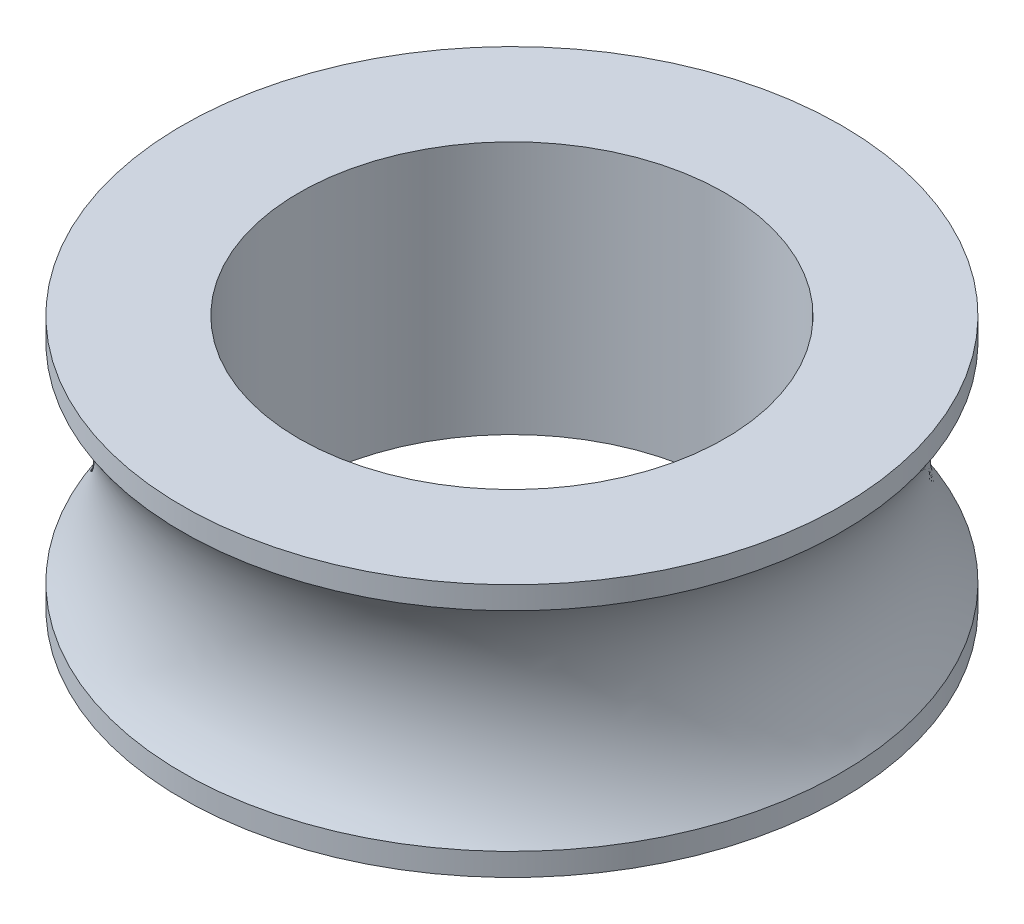
SolidWorks part; units mm, degrees
ref_plane "前视基准面" through (0, 0, 0) normal (0, 0, 1) x (1, 0, 0)
ref_plane "上视基准面" through (0, 0, 0) normal (0, 1, 0) x (1, 0, 0)
ref_plane "右视基准面" through (0, 0, 0) normal (1, 0, 0) x (0, 0, -1)
sketch "草图1" plane through (0, 0, 0) normal (0, 0, 1) x (1, 0, 0)
  line L0 (39, 27.3288) -> (39, 30)
  line L1 (0, 0) -> (39, 0)
  line L2 (0, 0) -> (0, 30)
  line L3 (0, 30) -> (39, 30)
  line L4 (39, 0) -> (39, 2.6712)
  arc A0 (39, 2.6712) -> (39, 27.3288) centre (56, 15) cw
  point P15 (35, 15)
  dimension "D3" = 21
  dimension "D1" = 30
  dimension "D2" = 39
  dimension "D4" = 35
revolve "旋转1" add sketch "草图1" angle 360 about L2
sketch "草图2" plane through (0, 30, 0) normal (0, 1, 0) x (1, 0, 0)
  circle A0 centre (0, 0) radius 25.2
  dimension "D1" = 50.4
extrude "切除-拉伸1" cut sketch "草图2" against normal through all
